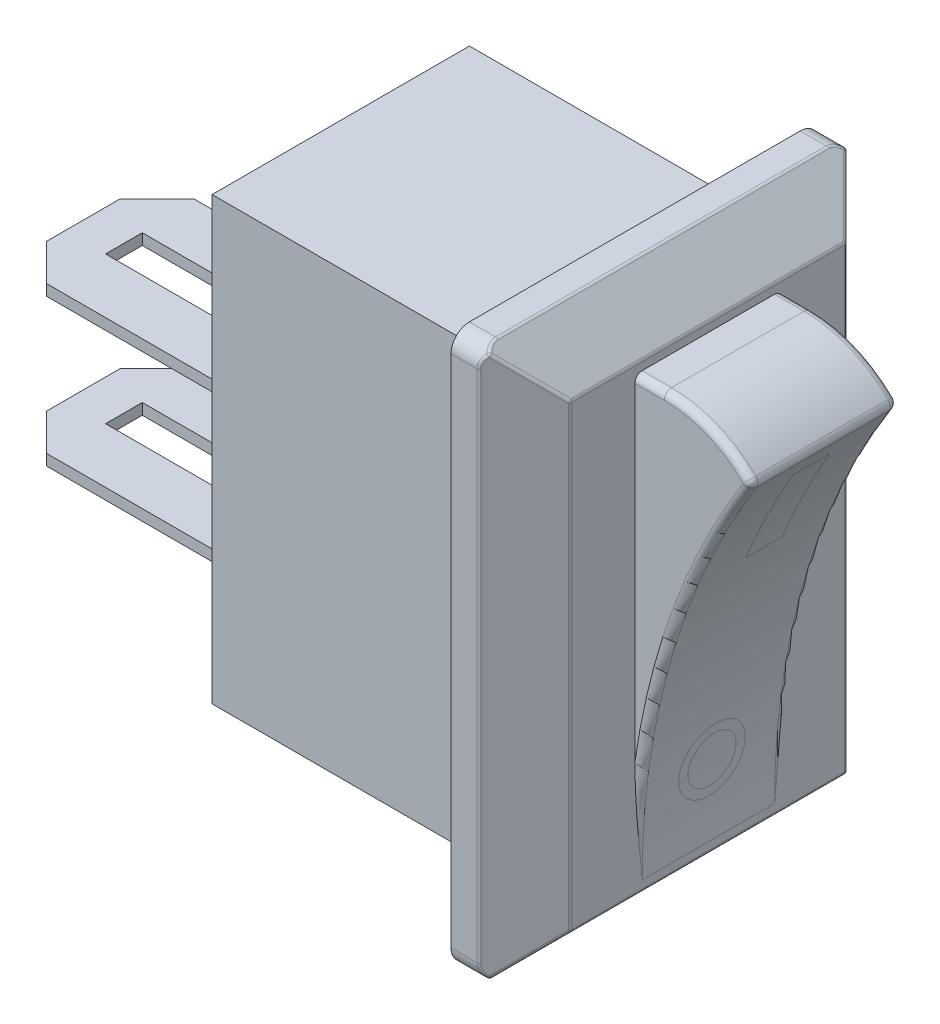
SolidWorks part; units mm, degrees
ref_plane "Front Plane" through (0, 0, 0) normal (0, 0, 1) x (1, 0, 0)
ref_plane "Top Plane" through (0, 0, 0) normal (0, 1, 0) x (1, 0, 0)
ref_plane "Right Plane" through (0, 0, 0) normal (1, 0, 0) x (0, 0, -1)
sketch "Sketch1" plane through (0, 0, 0) normal (1, 0, 0) x (0, 0, -1)
  line L1 (-3.5, 6) -> (3.5, 6)
  line L2 (-3.5, 6) -> (-3.5, -6)
  line L3 (-3.5, -6) -> (3.5, -6)
  line L4 (3.5, 6) -> (3.5, -6)
  line L5 (-3.5, 6) -> (3.5, -6) construction
  line L6 (-3.5, -6) -> (3.5, 6) construction
  point P0 (0, 0)
  dimension "D1" = 7
  dimension "D2" = 12
extrude "Boss-Extrude1" add sketch "Sketch1" along normal blind 8
sketch "Sketch3" plane through (8, 0, 0) normal (1, 0, 0) x (0, 0, -1)
  line L1 (-5, 7.5) -> (5, 7.5)
  line L2 (-5, 7.5) -> (-5, -7.5)
  line L3 (-5, -7.5) -> (5, -7.5)
  line L4 (5, 7.5) -> (5, -7.5)
  line L5 (-5, 7.5) -> (5, -7.5) construction
  line L6 (-5, -7.5) -> (5, 7.5) construction
  point P0 (0, 0)
  dimension "D1" = 15
  dimension "D2" = 10
extrude "Boss-Extrude3" add sketch "Sketch3" along normal blind 2
sketch "Sketch4" plane through (0, 0, 0) normal (0, 0, 1) x (1, 0, 0)
  line L0 (10, 6) -> (10.8, 6)
  line L1 (10, 7.5) -> (10, -7.5) construction
  line L2 (10, 6) -> (10, -6)
  arc A0 (10.8, 6) -> (13.2036, 4.9484) centre (10.8, 2.7273) cw
  arc A1 (13.2036, 4.9484) -> (10, -6) centre (30.3104, -6) ccw
  point P6 (10, 0)
  dimension "D1" = 12
  dimension "D3" = 3.2727
  dimension "D4" = 20.3104
  dimension "D2" = 0.8
extrude "Boss-Extrude4" add sketch "Sketch4" along normal mid plane 4
fillet "Fillet1" radius 0.5 4 edges at (9, -7.5, -5) (9, -7.5, 5) (9, 7.5, -5) (9, 7.5, 5)
chamfer "Chamfer1" distance 1.25 angle 45 4 edges at (10, 0, 5) (10, 7.5, 0) (10, 0, -5) (10, -7.5, 0)
sketch "Sketch5" plane through (0, 0, 0) normal (1, 0, 0) x (0, 0, -1)
  line L1 (-0.5, 4.3) -> (0.5, 4.3)
  line L2 (-0.5, 4.3) -> (-0.5, 1.7)
  line L3 (-0.5, 1.7) -> (0.5, 1.7)
  line L4 (0.5, 4.3) -> (0.5, 1.7)
  line L5 (-0.5, 4.3) -> (0.5, 1.7) construction
  line L6 (-0.5, 1.7) -> (0.5, 4.3) construction
  circle A0 centre (0, -4) radius 0.65
  circle A1 centre (0, -4) radius 0.9
  point P5 (0, 3)
  dimension "D3" = 1.8
  dimension "D2" = 4
  dimension "D4" = 1
  dimension "D5" = 2.6
  dimension "D6" = 3
  dimension "D1" = 0.25
split line "Split Line1"
fillet "Fillet2" radius 0.2 7 edges at (10.4, 6, 2) (10.4, 6, -2) (12.1118, 5.7256, 2) (12.1118, 5.7256, -2) (10.8173, -0.2963, 2) (10.8173, -0.2963, -2) (13.2036, 4.9484, 0)
fillet "Fillet3" radius 0.1 20 edges at (8.7881, 7.1913, 4.9619) (10, 0, 3.75) (8.7881, -7.1913, 4.9619) (8.75, 0, 5) (10, 6.25, 0) (9.4482, 6.8018, 4.3018) (8.7881, 7.4619, 4.6913) (8.75, 7.5, 0) (8.7881, 7.4619, -4.6913) (10, 0, -3.75) (9.4482, 6.8018, -4.3018) (8.7881, 7.1913, -4.9619) (8.75, 0, -5) (8.7881, -7.1913, -4.9619) (8.7881, -7.4619, 4.6913) (9.4482, -6.8018, 4.3018) (10, -6.25, 0) (9.4482, -6.8018, -4.3018) (8.7881, -7.4619, -4.6913) (8.75, -7.5, 0)
sketch "Sketch2" plane through (0, 0, 0) normal (-1, 0, 0) x (0, 0, 1)
  line L17 (-2, 0.75) -> (2, 0.75)
  line L18 (-2, 0.75) -> (-2, 0.25)
  line L23 (-2, 0.25) -> (2, 0.25)
  line L24 (2, 0.75) -> (2, 0.25)
  line L29 (-2, 0.75) -> (2, 0.25) construction
  line L30 (-2, 0.25) -> (2, 0.75) construction
  line L35 (-2, -0.25) -> (2, -0.25)
  line L36 (-2, -0.25) -> (-2, -0.75)
  line L41 (-2, -0.75) -> (2, -0.75)
  line L42 (2, -0.25) -> (2, -0.75)
  line L47 (-2, -0.25) -> (2, -0.75) construction
  line L48 (-2, -0.75) -> (2, -0.25) construction
  point P0 (0, 0.5)
  point P5 (0, -0.5)
  point P10 (0, 0)
  dimension "D1" = 0.5
  dimension "D2" = 4
  dimension "D3" = 0.5
  dimension "D4" = 0.25
extrude "Boss-Extrude2" add sketch "Sketch2" along normal blind 1
sketch "Sketch8" plane through (0, 0, 0) normal (-1, 0, 0) x (0, 0, 1)
  line L0 (2, -0.25) -> (-2, -0.25) construction
  line L1 (-2, 0.15) -> (2, 0.15)
  line L2 (-2, 0.15) -> (-2, -0.15)
  line L3 (-2, -0.15) -> (2, -0.15)
  line L4 (2, 0.15) -> (2, -0.15)
  line L5 (-2, 0.15) -> (2, -0.15) construction
  line L6 (-2, -0.15) -> (2, 0.15) construction
  line L7 (2, -0.25) -> (-2, -0.25) construction
  point P0 (0, 0)
  dimension "D1" = 0.1
extrude "Boss-Extrude5" add sketch "Sketch8" along normal blind 7
chamfer "Chamfer2" distance 1 angle 45 2 edges at (-7, 0, -2) (-7, 0, 2)
sketch "Sketch7" plane through (0, 0.15, 0) normal (0, 1, 0) x (1, 0, 0)
  line L0 (-7, 0) -> (-5.9, 0) construction
  line L1 (-2.9, 0.5) -> (-5.9, 0.5)
  line L2 (-2.9, 0.5) -> (-2.9, -0.5)
  line L3 (-2.9, -0.5) -> (-5.9, -0.5)
  line L4 (-5.9, 0.5) -> (-5.9, -0.5)
  line L8 (-7, -1) -> (-7, 1) construction
  dimension "D1" = 1.1
  dimension "D2" = 3
  dimension "D3" = 1
extrude "Cut-Extrude3" cut sketch "Sketch7" against normal up to next contours L1 L4 L3 L2
pattern_linear "LPattern1" count 2 spacing 4 along (0, -1, 0) of "Boss-Extrude2", "Boss-Extrude5", "Cut-Extrude3", "Chamfer2"
pattern_linear "LPattern2" count 2 spacing 4 along (0, 1, 0) of "Boss-Extrude2"
